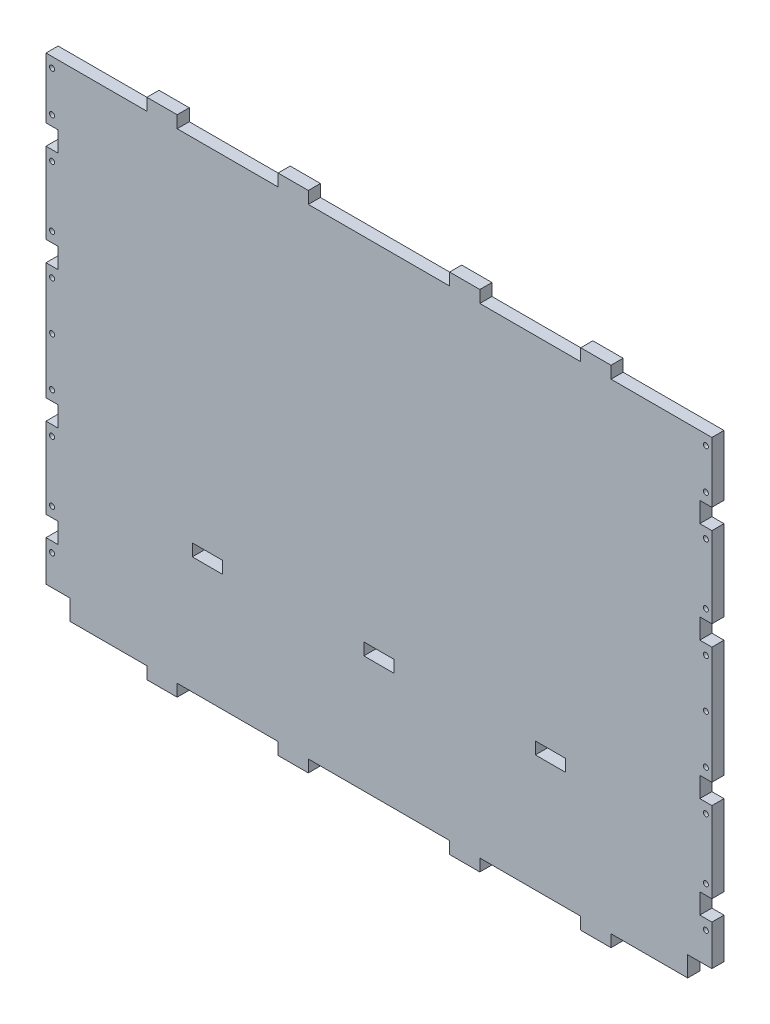
SolidWorks part; units mm, degrees
ref_plane "Plan de face" through (0, 0, 0) normal (0, 0, 1) x (1, 0, 0)
ref_plane "Plan de dessus" through (0, 0, 0) normal (0, 1, 0) x (1, 0, 0)
ref_plane "Plan de droite" through (0, 0, 0) normal (1, 0, 0) x (0, 0, -1)
sketch "Esquisse1" plane through (0, 0, 0) normal (0, 0, 1) x (1, 0, 0)
  line L0 (97.3951, 0) -> (-118.5049, 0) construction
  line L1 (-165, 119) -> (165, 119)
  line L2 (-165, 119) -> (-165, -119)
  line L3 (-165, -119) -> (165, -119)
  line L4 (165, 119) -> (165, -119)
  line L5 (0, 79.3588) -> (0, -79.3588) construction
  line L6 (-92.5, -55) -> (-77.5, -55)
  line L7 (-92.5, -55) -> (-92.5, -61)
  line L8 (-92.5, -61) -> (-77.5, -61)
  line L9 (-77.5, -55) -> (-77.5, -61)
  line L10 (-7.5, -55) -> (7.5, -55)
  line L11 (-7.5, -55) -> (-7.5, -61)
  line L12 (-7.5, -61) -> (7.5, -61)
  line L13 (7.5, -55) -> (7.5, -61)
  line L14 (77.5, -55) -> (92.5, -55)
  line L15 (77.5, -55) -> (77.5, -61)
  line L16 (77.5, -61) -> (92.5, -61)
  line L17 (92.5, -55) -> (92.5, -61)
  dimension "D1" = 238
  dimension "D2" = 330
  dimension "D3" = 165
  dimension "D4" = 119
  dimension "D5" = 15
  dimension "D6" = 6
  dimension "D7" = 6
  dimension "D8" = 15
  dimension "D9" = 6
  dimension "D10" = 15
  dimension "D11" = 70
  dimension "D12" = 70
  dimension "D13" = 58
  dimension "D14" = 72.5
extrude "Boss.-Extru.1" add sketch "Esquisse1" along normal blind 6
sketch "Esquisse2" plane through (0, 0, 6) normal (0, 0, 1) x (1, 0, 0)
  line L0 (243.146, 0) -> (-260.0003, 0) construction
  line L1 (0, 180.4713) -> (0, -129.6072) construction
  line L2 (165, 119) -> (-165, 119) construction
  line L3 (-115, 119) -> (-100, 119)
  line L4 (-115, 119) -> (-115, 125)
  line L5 (-115, 125) -> (-100, 125)
  line L6 (-100, 119) -> (-100, 125)
  line L7 (-165, 119) -> (-165, -119) construction
  line L8 (-50, 119) -> (-35, 119)
  line L9 (-50, 119) -> (-50, 125)
  line L10 (-50, 125) -> (-35, 125)
  line L11 (-35, 119) -> (-35, 125)
  line L12 (35, 119) -> (35, 125)
  line L13 (50, 125) -> (35, 125)
  line L14 (50, 119) -> (50, 125)
  line L15 (50, 119) -> (35, 119)
  line L16 (100, 119) -> (100, 125)
  line L17 (115, 125) -> (100, 125)
  line L18 (115, 119) -> (115, 125)
  line L19 (115, 119) -> (100, 119)
  line L20 (-115, 119) -> (-100, 119)
  line L21 (-115, 119) -> (-115, 125)
  line L22 (-115, 125) -> (-100, 125)
  line L23 (-100, 119) -> (-100, 125)
  line L24 (-50, 119) -> (-35, 119)
  line L25 (-50, 119) -> (-50, 125)
  line L26 (-50, 125) -> (-35, 125)
  line L27 (-35, 119) -> (-35, 125)
  line L28 (35, 119) -> (35, 125)
  line L29 (50, 125) -> (35, 125)
  line L30 (50, 119) -> (50, 125)
  line L31 (50, 119) -> (35, 119)
  line L32 (100, 119) -> (100, 125)
  line L33 (115, 125) -> (100, 125)
  line L34 (115, 119) -> (115, 125)
  line L35 (115, 119) -> (100, 119)
  line L36 (115, -119) -> (100, -119)
  line L37 (115, -119) -> (115, -125)
  line L38 (115, -125) -> (100, -125)
  line L39 (100, -119) -> (100, -125)
  line L40 (50, -119) -> (35, -119)
  line L41 (50, -119) -> (50, -125)
  line L42 (50, -125) -> (35, -125)
  line L43 (35, -119) -> (35, -125)
  line L44 (-35, -119) -> (-35, -125)
  line L45 (-50, -125) -> (-35, -125)
  line L46 (-50, -119) -> (-50, -125)
  line L47 (-50, -119) -> (-35, -119)
  line L48 (-100, -119) -> (-100, -125)
  line L49 (-115, -125) -> (-100, -125)
  line L50 (-115, -119) -> (-115, -125)
  line L51 (-115, -119) -> (-100, -119)
  line L52 (115, -119) -> (100, -119)
  line L53 (115, -119) -> (115, -125)
  line L54 (115, -125) -> (100, -125)
  line L55 (100, -119) -> (100, -125)
  line L56 (50, -119) -> (35, -119)
  line L57 (50, -119) -> (50, -125)
  line L58 (50, -125) -> (35, -125)
  line L59 (35, -119) -> (35, -125)
  line L60 (-35, -119) -> (-35, -125)
  line L61 (-50, -125) -> (-35, -125)
  line L62 (-50, -119) -> (-50, -125)
  line L63 (-50, -119) -> (-35, -119)
  line L64 (-100, -119) -> (-100, -125)
  line L65 (-115, -125) -> (-100, -125)
  line L66 (-115, -119) -> (-115, -125)
  line L67 (-115, -119) -> (-100, -119)
  line M9 (-165, -119) -> (165, -119)
  line M11 (165, 119) -> (-165, 119)
  dimension "D1" = 6
  dimension "D2" = 6
  dimension "D3" = 15
  dimension "D4" = 15
  dimension "D5" = 50
  dimension "D6" = 50
extrude "Boss.-Extru.2" add sketch "Esquisse2" against normal blind 6 contours L6 L5 L4 M11 | L11 L10 L9 M11 | L14 L13 L12 M11 | L18 L17 L16 M11 | L39 L38 L37 M9 | L43 L42 L41 M9 | L46 L45 L44 M9 | L50 L49 L48 M9 region at (-107.5, 122, 6) region at (107.5, 122, 6) region at (42.5, 122, 6) region at (-42.5, 122, 6) region at (107.5, -122, 6) region at (-107.5, -122, 6) region at (-42.5, -122, 6) region at (42.5, -122, 6)
sketch "Esquisse3" plane through (0, 0, 6) normal (0, 0, 1) x (1, 0, 0)
  line L0 (-165, 119) -> (-165, -119) construction
  line L1 (-165, 79) -> (-159, 79)
  line L2 (-165, 79) -> (-165, 89)
  line L3 (-165, 89) -> (-159, 89)
  line L4 (-159, 79) -> (-159, 89)
  line L5 (234.1368, 0) -> (-337.9213, 0) construction
  line L6 (-165, 39) -> (-159, 39)
  line L7 (-165, 39) -> (-165, 29)
  line L8 (-165, 29) -> (-159, 29)
  line L9 (-159, 39) -> (-159, 29)
  line L10 (0, 279.7488) -> (0, -188.1201) construction
  line L11 (-115, 119) -> (-165, 119) construction
  line L12 (-159, -39) -> (-159, -29)
  line L13 (-165, -29) -> (-159, -29)
  line L14 (-165, -39) -> (-165, -29)
  line L15 (-165, -39) -> (-159, -39)
  line L16 (-159, -79) -> (-159, -89)
  line L17 (-165, -89) -> (-159, -89)
  line L18 (-165, -79) -> (-165, -89)
  line L19 (-165, -79) -> (-159, -79)
  line L20 (165, -79) -> (159, -79)
  line L21 (165, -79) -> (165, -89)
  line L22 (165, -89) -> (159, -89)
  line L23 (159, -79) -> (159, -89)
  line L24 (165, -39) -> (159, -39)
  line L25 (165, -39) -> (165, -29)
  line L26 (165, -29) -> (159, -29)
  line L27 (159, -39) -> (159, -29)
  line L28 (159, 39) -> (159, 29)
  line L29 (165, 29) -> (159, 29)
  line L30 (165, 39) -> (165, 29)
  line L31 (165, 39) -> (159, 39)
  line L32 (159, 79) -> (159, 89)
  line L33 (165, 89) -> (159, 89)
  line L34 (165, 79) -> (165, 89)
  line L35 (165, 79) -> (159, 79)
  line L36 (153, -119) -> (153, -109)
  line L37 (-165, -119) -> (-153, -119)
  line L38 (-165, -119) -> (-165, -109)
  line L39 (-165, -109) -> (-153, -109)
  line L40 (-153, -119) -> (-153, -109)
  line L41 (165, -109) -> (153, -109)
  line L42 (165, -119) -> (165, -109)
  line L43 (165, -119) -> (153, -119)
  dimension "D1" = 40
  dimension "D2" = 6
  dimension "D3" = 6
  dimension "D4" = 10
  dimension "D5" = 10
  dimension "D6" = 30
  dimension "D7" = 12
  dimension "D8" = 10
extrude "Enlèv. mat.-Extru.1" cut sketch "Esquisse3" against normal blind 6
sketch "Esquisse4" plane through (0, 0, 6) normal (0, 0, 1) x (1, 0, 0)
  line L0 (-162, 121.7279) -> (-162, -131.0602) construction
  line L1 (0, 158.5579) -> (0, -182.4489) construction
  line L2 (-115, 119) -> (-165, 119) construction
  line L4 (-159, 89) -> (-165, 89) construction
  line L5 (-165, 119) -> (-165, 89) construction
  line L6 (-165, 79) -> (-159, 79) construction
  line L7 (-159, 39) -> (-165, 39) construction
  line L8 (-165, 29) -> (-159, 29) construction
  line L9 (-159, -29) -> (-165, -29) construction
  line L12 (-165, -39) -> (-159, -39) construction
  line L13 (-159, -79) -> (-165, -79) construction
  line L14 (-165, -89) -> (-159, -89) construction
  line L16 (162, 121.7279) -> (162, -131.0602) construction
  circle A0 centre (-162, 114) radius 1.25
  circle A1 centre (-162, 94) radius 1.25
  circle A2 centre (-162, 74) radius 1.25
  circle A3 centre (-162, 44) radius 1.25
  circle A4 centre (-162, 24) radius 1.25
  circle A5 centre (-162, 0) radius 1.25
  circle A6 centre (-162, -24) radius 1.25
  circle A7 centre (-162, -44) radius 1.25
  circle A8 centre (-162, -74) radius 1.25
  circle A9 centre (-162, -94) radius 1.25
  circle A12 centre (162, -94) radius 1.25
  circle A13 centre (162, -74) radius 1.25
  circle A14 centre (162, -44) radius 1.25
  circle A15 centre (162, -24) radius 1.25
  circle A16 centre (162, 0) radius 1.25
  circle A17 centre (162, 24) radius 1.25
  circle A18 centre (162, 44) radius 1.25
  circle A19 centre (162, 74) radius 1.25
  circle A20 centre (162, 94) radius 1.25
  circle A21 centre (162, 114) radius 1.25
  dimension "D1" = 2.5
  dimension "D2" = 2.5
  dimension "D3" = 2.5
  dimension "D4" = 2.5
  dimension "D5" = 2.5
  dimension "D6" = 2.5
  dimension "D7" = 2.5
  dimension "D8" = 2.5
  dimension "D9" = 2.5
  dimension "D10" = 2.5
  dimension "D12" = 5
  dimension "D13" = 5
  dimension "D15" = 5
  dimension "D16" = 5
  dimension "D17" = 5
  dimension "D19" = 29
  dimension "D20" = 5
  dimension "D21" = 5
  dimension "D14" = 3
  dimension "D18" = 5
  dimension "D22" = 5
extrude "Enlèv. mat.-Extru.2" cut sketch "Esquisse4" against normal blind 6
equation "\"D3@Esquisse1\"=\"D2@Esquisse1\"/2"
equation "\"D4@Esquisse1\"=\"D1@Esquisse1\"/2"
